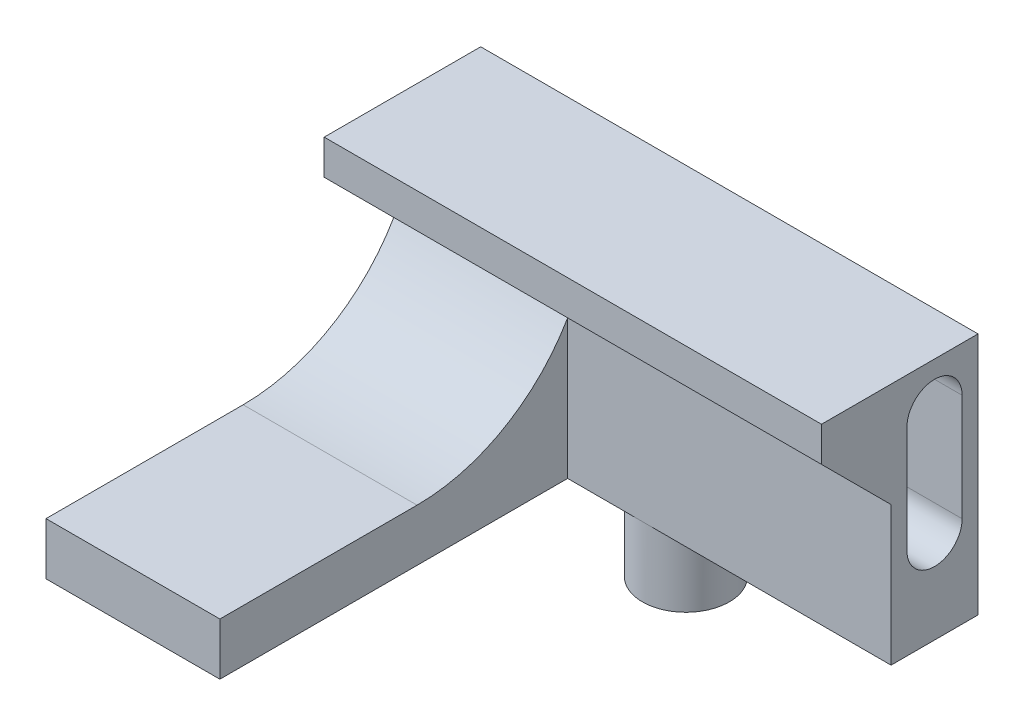
SolidWorks part; units mm, degrees
ref_plane "Front Plane" through (0, 0, 0) normal (0, 0, 1) x (1, 0, 0)
ref_plane "Top Plane" through (0, 0, 0) normal (0, 1, 0) x (1, 0, 0)
ref_plane "Right Plane" through (0, 0, 0) normal (1, 0, 0) x (0, 0, -1)
sketch "Sketch1" plane through (0, 0, 0) normal (0, 1, 0) x (1, 0, 0)
  line L1 (-14.3, -2.5) -> (14.3, -2.5)
  line L2 (-14.3, -2.5) -> (-14.3, 2.5)
  line L3 (-14.3, 2.5) -> (14.3, 2.5)
  line L4 (14.3, -2.5) -> (14.3, 2.5)
  line L5 (-14.3, -2.5) -> (14.3, 2.5) construction
  line L6 (-14.3, 2.5) -> (14.3, -2.5) construction
  point P0 (0, 0)
  dimension "D1" = 28.6
  dimension "D2" = 5
extrude "Boss-Extrude1" add sketch "Sketch1" along normal blind 14 contours L1 L4 L3 L2
sketch "Sketch2" plane through (14.3, 0, 0) normal (1, 0, 0) x (0, 0, -1)
  line L0 (2.5, 14) -> (-2.5, 0) construction
  line L1 (0, 5.25) -> (0, 11.4) construction
  line L2 (-1.5875, 5.25) -> (-1.5875, 11.4)
  line L3 (1.5875, 5.25) -> (1.5875, 11.4)
  arc A0 (-1.5875, 5.25) -> (1.5875, 5.25) centre (0, 5.25) ccw
  arc A1 (1.5875, 11.4) -> (-1.5875, 11.4) centre (0, 11.4) ccw
  point P6 (0, 8.325)
  dimension "D1" = 6.15
  dimension "D2" = 3.175
extrude "Cut-Extrude1" cut sketch "Sketch2" against normal blind 4
sketch "Sketch5" plane through (0, 0, 0) normal (0, -1, 0) x (1, 0, 0)
  circle A0 centre (0, 0) radius 2.5
extrude "Boss-Extrude4" add sketch "Sketch5" along normal blind 4
sketch "Sketch6" plane through (14.3, 0, 0) normal (1, 0, 0) x (0, 0, -1)
  line L0 (-2.5, 14) -> (-6.5, 14)
  line L1 (-6.5, 14) -> (-6.5, 12)
  line L2 (-6.5, 12) -> (-2.5, 8)
  line L3 (-2.5, 14) -> (-2.5, 0) construction
  line L4 (-2.5, 8) -> (-2.5, 14)
  dimension "D1" = 2
  dimension "D2" = 4
  dimension "D3" = 45
extrude "Boss-Extrude5" add sketch "Sketch6" against normal up to surface (28.6 mm away) up to face at (-14.3, 7, 0)
mirror "Mirror1" about plane through (0, 0, 0) normal (1, 0, 0) of "Cut-Extrude1"
sketch "Sketch7" plane through (-14.3, 0, 0) normal (-1, 0, 0) x (0, 0, 1)
  line L0 (2.5, 0) -> (22.5, 0)
  line L1 (22.5, 0) -> (22.5, 3)
  line L2 (22.5, 3) -> (2.5, 3)
  line L3 (2.5, 8) -> (2.5, 0) construction
  line L4 (2.5, 0) -> (2.5, 3)
  dimension "D1" = 3
  dimension "D2" = 20
extrude "Boss-Extrude6" add sketch "Sketch7" against normal blind 10 contours L2 L4 L0 L1
fillet "Fillet1" radius 10 1 edges at (-9.3, 3, 2.5)
